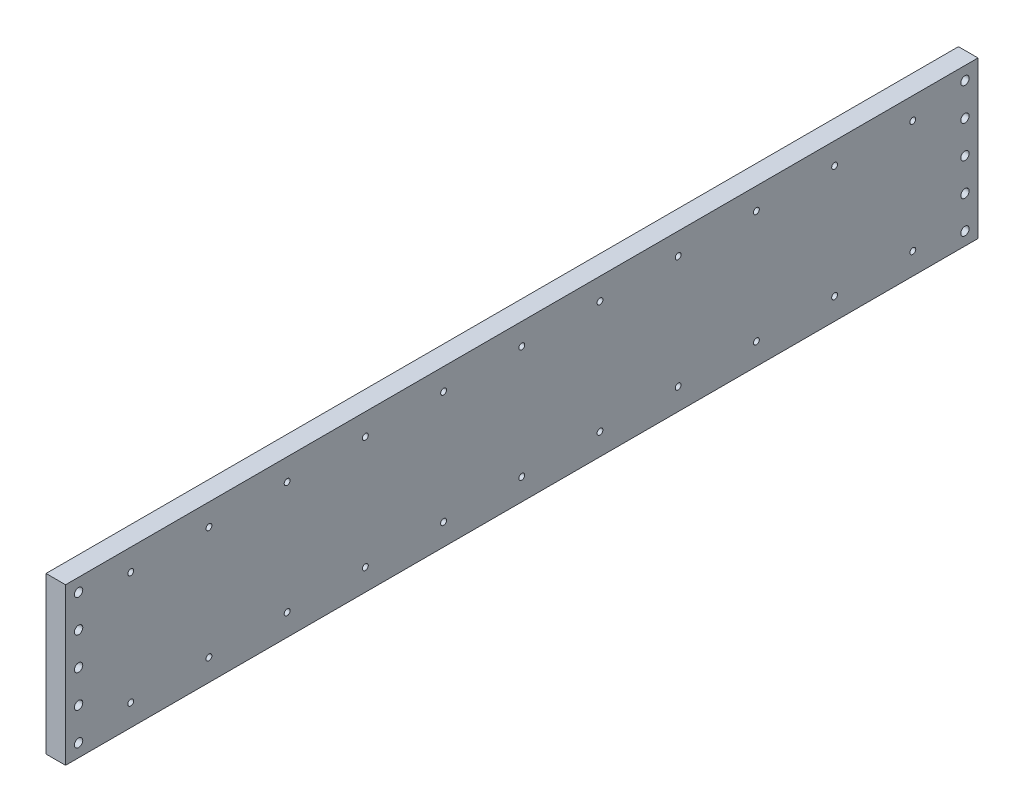
SolidWorks part; units mm, degrees
ref_plane "Front Plane" through (0, 0, 0) normal (0, 0, 1) x (1, 0, 0)
ref_plane "Top Plane" through (0, 0, 0) normal (0, 1, 0) x (1, 0, 0)
ref_plane "Right Plane" through (0, 0, 0) normal (1, 0, 0) x (0, 0, -1)
sketch "Sketch2" plane through (0, 0, 0) normal (0, 0, 1) x (1, 0, 0)
  line L0 (-15, 0) -> (0, 0)
  line L3 (0, 0) -> (0, -120)
  line L4 (0, -120) -> (-15, -120)
  line L5 (-15, -120) -> (-15, 0)
  dimension "D1" = 120
  dimension "D2" = 15
extrude "Boss-Extrude1" add sketch "Sketch2" along normal blind 700
sketch "Sketch7" plane through (0, 0, 0) normal (1, 0, 0) x (0, 0, -1)
  line L0 (-700, -60) -> (0, -60) construction
  line L2 (-700, -16.7) -> (0, -16.7) construction
  line L4 (-700, 0) -> (0, 0) construction
  line L5 (-700, -120) -> (-700, 0) construction
  point P4 (-50, -103.3)
  point P7 (-110, -103.3)
  point P8 (-170, -103.3)
  point P11 (-650, -16.7)
  point P13 (-590, -16.7)
  point P14 (-530, -16.7)
  point P15 (-470, -16.7)
  point P16 (-410, -16.7)
  point P17 (-350, -16.7)
  point P18 (-290, -16.7)
  point P19 (-230, -16.7)
  point P20 (-170, -16.7)
  point P29 (-110, -16.7)
  point P30 (-50, -16.7)
  point P32 (-230, -103.3)
  point P35 (-290, -103.3)
  point P36 (-350, -103.3)
  point P37 (-410, -103.3)
  point P38 (-470, -103.3)
  point P39 (-530, -103.3)
  point P40 (-590, -103.3)
  point P41 (-650, -103.3)
  dimension "D1" = 16.7
  dimension "D2" = 50
  dimension "D3" = 11
hole_wizard "Ø4.5 (4.5) Diameter Hole1" positions "3DSketch3" profile "Sketch8" hole size "Ø4.5" standard "ISO" end condition through all
sketch3d "3DSketch3"
  point P0 (0, -16.7, 650)
  point P3 (0, -16.7, 590)
  point P6 (0, -16.7, 530)
  point P9 (0, -16.7, 470)
  point P12 (0, -16.7, 410)
  point P15 (0, -16.7, 350)
  point P18 (0, -16.7, 290)
  point P21 (0, -16.7, 230)
  point P24 (0, -16.7, 170)
  point P54 (0, -16.7, 110)
  point P57 (0, -16.7, 50)
  point P64 (0, -103.3, 650)
  point P67 (0, -103.3, 590)
  point P70 (0, -103.3, 530)
  point P73 (0, -103.3, 470)
  point P76 (0, -103.3, 410)
  point P79 (0, -103.3, 350)
  point P82 (0, -103.3, 290)
  point P85 (0, -103.3, 230)
  point P88 (0, -103.3, 170)
  point P91 (0, -103.3, 110)
  point P94 (0, -103.3, 50)
sketch "Sketch8" plane through (0, -16.7, 650) normal (0, 1, 0) x (0, 0, -1)
  line L0 (0, 0) -> (0, 15)
  line L1 (0, 15) -> (2.25, 15)
  line L2 (2.25, 15) -> (2.25, 0)
  line L5 (2.25, 0) -> (0, 0)
  line L11 (0, -6.35) -> (0, 107.95) construction
  dimension "Thru Hole Dia." = 4.5
  dimension "Thru Hole Depth" = 15
sketch "Sketch12" plane through (-15, 0, 0) normal (1, 0, 0) x (0, 0, -1)
  line L0 (-690, 0) -> (-690, -120) construction
  line L1 (-700, 0) -> (0, 0) construction
  line L2 (-700, -120) -> (0, -120) construction
  line L3 (-700, -120) -> (-700, 0) construction
  line L4 (-700, -60) -> (-669.8028, -60) construction
  line L5 (-700, -60) -> (0, -60) construction
  line L6 (-350, 0) -> (-350, -120) construction
  point P13 (-690, -60)
  point P15 (-690, -85)
  point P16 (-690, -35)
  point P17 (-690, -10)
  point P18 (-690, -110)
  point P19 (-10, -110)
  point P20 (-10, -10)
  point P22 (-10, -35)
  point P23 (-10, -85)
  point P24 (-10, -60)
  dimension "D1" = 10
  dimension "D2" = 3
hole_wizard "CBORE for M6 SHCS1" positions "3DSketch7" profile "Sketch14" counterbore size "M6" standard "ANSI Metric" end condition through all
sketch3d "3DSketch7"
  line L0 (-15, 0, 690) -> (-15, -120, 690) construction
  point P0 (-15, -10, 690)
  point P3 (-15, -60, 690)
  point P7 (-15, -35, 690)
  point P10 (-15, -85, 690)
  point P13 (-15, -110, 690)
  point P16 (-15, -60, 690)
  point P18 (-15, -60, 690)
  point P20 (-15, -60, 690)
  point P22 (-15, -60, 690)
  point P25 (-15, -10, 10)
  point P28 (-15, -35, 10)
  point P31 (-15, -60, 10)
  point P34 (-15, -85, 10)
  point P37 (-15, -110, 10)
sketch "Sketch14" plane through (-15, -10, 690) normal (0, 1, 0) x (0, 0, 1)
  line L0 (0, 0) -> (0, 15)
  line L1 (0, 15) -> (3.2, 15)
  line L3 (3.2, 15) -> (3.2, 6)
  line L4 (3.2, 6) -> (5.5, 6)
  line L5 (5.5, 6) -> (5.5, 0)
  line L7 (5.5, 0) -> (0, 0)
  line L11 (0, -6.35) -> (0, 107.95) construction
  dimension "Thru Hole Dia." = 6.4
  dimension "Thru Hole Depth" = 15
  dimension "C'Bore Dia." = 11
  dimension "C'Bore Depth" = 6
